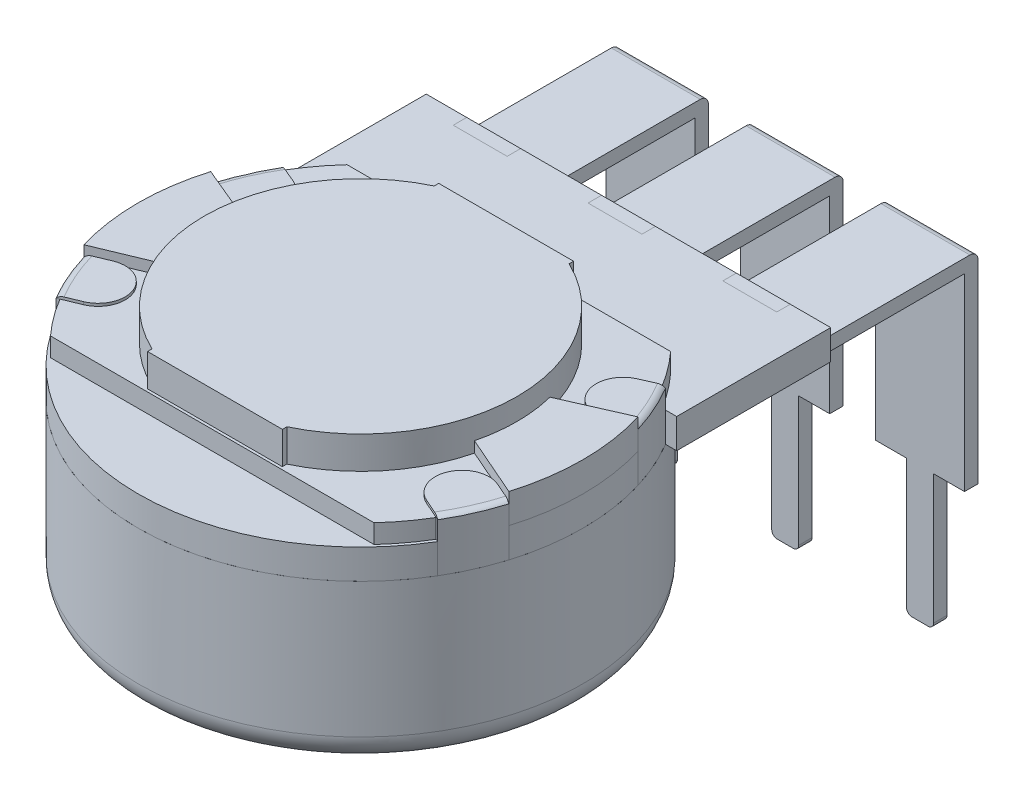
SolidWorks part; units mm, degrees
ref_plane "Front Plane" through (0, 0, 0) normal (0, 0, 1) x (1, 0, 0)
ref_plane "Top Plane" through (0, 0, 0) normal (0, 1, 0) x (1, 0, 0)
ref_plane "Right Plane" through (0, 0, 0) normal (1, 0, 0) x (0, 0, -1)
sketch "Sketch1" plane through (0, 0, 0) normal (0, 1, 0) x (1, 0, 0)
  circle A0 centre (0, 0) radius 8.25
  dimension "D1" = 16.5
extrude "Boss-Extrude1" add sketch "Sketch1" along normal blind 6
fillet "Fillet1" radius 1 1 edges at (0, 0, 8.25)
sketch "Sketch2" plane through (0, 6, 0) normal (0, 1, 0) x (1, 0, 0)
  line L0 (-6, 5.6624) -> (6, 5.6624)
  circle A0 centre (0, 0) radius 8.25 construction
  arc A1 (6, 5.6624) -> (-6, 5.6624) centre (0, 0) ccw
  dimension "D1" = 12
  dimension "D2" = 5.6624
extrude "Cut-Extrude1" cut sketch "Sketch2" against normal blind 2
sketch "Sketch3" plane through (0, 6, 0) normal (0, 1, 0) x (1, 0, 0)
  circle A0 centre (0, 0) radius 8
  dimension "D1" = 16
extrude "Cut-Extrude2" cut sketch "Sketch3" against normal blind 5.6
sketch "Sketch4" plane through (0, 6, 0) normal (0, 1, 0) x (1, 0, 0)
  line L6 (-7.5, 3.4369) -> (-7.5, 9.9369)
  line L7 (-7.5, 9.9369) -> (7.5, 9.9369)
  line L8 (7.5, 3.4369) -> (7.5, 9.9369)
  arc A1 (-6, 5.6624) -> (6, 5.6624) centre (0, 0) ccw construction
  arc A2 (-7.5, 3.4369) -> (7.5, 3.4369) centre (0, 0) ccw
  dimension "D1" = 15
  dimension "D2" = 7.5
  dimension "D3" = 6.5
extrude "Boss-Extrude2" add sketch "Sketch4" along normal blind 1.1 separate body
sketch "Sketch6" plane through (0, 7.1, 0) normal (0, 1, 0) x (1, 0, 0)
  line L1 (-6, 5.5) -> (6, 5.5)
  line L3 (-6, -5.5) -> (6, -5.5)
  arc A0 (-6, 5.5) -> (-6, -5.5) centre (0, 0) ccw
  arc A1 (6, -5.5) -> (6, 5.5) centre (0, 0) ccw
  dimension "D1" = 11
  dimension "D2" = 5.5
  dimension "D3" = 12
  dimension "D4" = 11
extrude "Boss-Extrude3" add sketch "Sketch6" along normal blind 0.7 separate body
sketch "Sketch7" plane through (0, 7.8, 0) normal (0, 1, 0) x (1, 0, 0)
  line L0 (2.5, -5.4) -> (2.5, -5.2335)
  line L1 (-2.5, -5.4) -> (2.5, -5.4)
  line L3 (-2.5, 5.4) -> (2.5, 5.4)
  line L5 (-2.5, -5.4) -> (-2.5, -5.2335)
  line L6 (-2.5, 5.2335) -> (-2.5, 5.4)
  line L7 (2.5, 5.2335) -> (2.5, 5.4)
  arc A0 (-2.5, -5.2335) -> (-2.5, 5.2335) centre (0, 0) cw
  arc A1 (2.5, 5.2335) -> (2.5, -5.2335) centre (0, 0) cw
  dimension "D5" = 5.8
  dimension "D6" = 5.8
  dimension "D1" = 5
  dimension "D2" = 5.4
  dimension "D3" = 10.8
  dimension "D4" = 5.4
  dimension "D7" = 0.1665
  dimension "D8" = 0.1665
extrude "Boss-Extrude4" add sketch "Sketch7" along normal blind 1.2
sketch "Sketch11" plane through (0, 7.1, 0) normal (0, 1, 0) x (1, 0, 0)
  line L2 (-7.9082, 2.35) -> (-5.6294, 1.3965)
  line L3 (-7.9082, -2.35) -> (-5.6276, -1.4035)
  line L4 (7.7928, 2.35) -> (5.6294, 1.3965)
  line L6 (5.6278, -1.4028) -> (7.7928, -2.35)
  arc A0 (-7.5, 3.4369) -> (7.5, 3.4369) centre (0, 0) ccw construction
  arc A1 (-2.5, 5.2335) -> (-2.5, -5.2335) centre (0, 0) ccw construction
  arc A2 (-7.9082, 2.35) -> (-7.9082, -2.35) centre (0, 0) ccw
  arc A3 (-5.6294, 1.3965) -> (-5.6276, -1.4035) centre (0, 0) ccw
  arc A4 (6, -5.5) -> (6, 5.5) centre (0, 0) ccw construction
  arc A5 (2.5, -5.2335) -> (2.5, 5.2335) centre (0, 0) ccw construction
  arc A6 (7.7928, 2.35) -> (7.7928, -2.35) centre (0, 0) cw
  arc A7 (5.6278, -1.4028) -> (5.6294, 1.3965) centre (0, 0) ccw
  dimension "D1" = 4.7
  dimension "D3" = 2.8
extrude "Cut-Extrude4" cut sketch "Sketch11" along normal blind 0.7
sketch "Sketch12" plane through (0, 7.1, 0) normal (0, 1, 0) x (1, 0, 0)
  line L0 (-5.6276, -1.4035) -> (-7.9082, -2.3502)
  line L2 (-7.9082, 2.3502) -> (-5.6294, 1.3965)
  line L4 (5.6294, 1.3965) -> (7.8947, 2.3949)
  line L5 (5.6278, -1.4028) -> (7.8947, -2.3949)
  arc A0 (-2.5, 5.2335) -> (-2.5, -5.2335) centre (0, 0) ccw construction
  arc A1 (-5.6276, -1.4035) -> (-2.5, -5.2335) centre (0, 0) ccw construction
  arc A2 (-7.5, 3.4369) -> (7.5, 3.4369) centre (0, 0) ccw construction
  arc A3 (-5.6294, 1.3965) -> (-5.6276, -1.4035) centre (0, 0) ccw
  arc A4 (-7.9082, 2.3502) -> (-7.9082, -2.3502) centre (0, 0) ccw
  arc A5 (5.6294, 1.3965) -> (5.6278, -1.4028) centre (0, 0) cw
  arc A6 (7.8947, -2.3949) -> (7.8947, 2.3949) centre (0, 0) ccw
extrude "Boss-Extrude6" add sketch "Sketch12" along normal blind 1.1 separate body
sketch "Sketch14" plane through (0, 7.8, 0) normal (0, 1, 0) x (1, 0, 0)
  line L0 (7.8947, -2.3949) -> (7.7928, -2.35)
  line L1 (5.6278, -1.4028) -> (7.7928, -2.35) construction
  line L2 (7.0864, -4.2243) -> (6.9781, -4.1766)
  line L3 (6.9781, -4.1766) -> (7.7928, -2.35)
  line L4 (-7.9082, -2.3502) -> (-7.8055, -2.3074)
  line L5 (-7.8055, -2.3074) -> (-7.0004, -4.1381)
  line L6 (-7.0004, -4.1381) -> (-7.1102, -4.1842)
  line L7 (-7.1102, 4.1842) -> (-7.5, 4.1842)
  line L8 (-7.5, 9.9369) -> (-7.5, 3.4369) construction
  line L9 (-7.5, 4.1842) -> (-7.5, 3.4369)
  line L10 (-7.1102, 4.1842) -> (-7.008, 4.124)
  line L11 (-7.008, 4.124) -> (-7.8056, 2.3071)
  line L12 (-7.8056, 2.3071) -> (-7.9082, 2.3502)
  line L13 (-5.6294, 1.3965) -> (-7.9082, 2.3502) construction
  line L14 (7.0864, 4.2243) -> (7.5, 4.2243)
  line L16 (7.5, 3.4369) -> (7.5, 9.9369) construction
  line L22 (7.5, 4.2243) -> (7.5, 3.4369)
  line L23 (7.0864, 4.2243) -> (6.9858, 4.1644)
  line L24 (6.9858, 4.1644) -> (7.7928, 2.35)
  line L25 (7.8947, 2.3949) -> (5.6294, 1.3965) construction
  line L26 (7.7928, 2.35) -> (5.6294, 1.3965) construction
  line L27 (7.7928, 2.35) -> (7.8947, 2.3949)
  arc A0 (7.8947, -2.3949) -> (7.0864, -4.2243) centre (0, 0) cw
  arc A1 (-7.5, 3.4369) -> (7.5, 3.4369) centre (0, 0) ccw construction
  arc A2 (6, -5.5) -> (7.7928, -2.35) centre (0, 0) ccw construction
  arc A3 (-7.9082, -2.3502) -> (-7.1102, -4.1842) centre (0, 0) ccw
  arc A5 (-7.5, 3.4369) -> (-7.9082, 2.3502) centre (0, 0) ccw
  arc A9 (7.8947, 2.3949) -> (7.5, 3.4369) centre (0, 0) ccw
  point P49 (0, 0)
  dimension "D1" = 2
  dimension "D2" = 2
  dimension "D3" = 2
  dimension "D4" = 2
  dimension "D5" = 0.1191
  dimension "D6" = 2
  dimension "D7" = 1.8169
  dimension "D8" = 0.3898
  dimension "D9" = 2
extrude "Cut-Extrude5" cut sketch "Sketch14" against normal blind 1.8
sketch "Sketch16" plane through (0, 6, 0) normal (0, 1, 0) x (1, 0, 0)
  line L0 (6.9781, -4.1766) -> (7.0864, -4.2243) construction
  line L1 (7.0864, -4.2243) -> (6.9845, -4.1794)
  line L2 (6.9845, -4.1794) -> (7.7927, -2.3503)
  line L3 (7.7927, -2.3503) -> (7.8947, -2.3949)
  line L4 (7.8947, 2.3949) -> (7.7928, 2.35)
  line L5 (7.8947, 2.3949) -> (5.6294, 1.3965) construction
  line L6 (6.9858, 4.1644) -> (7.7928, 2.35) construction
  line L7 (7.7928, 2.35) -> (6.9858, 4.1644)
  line L8 (6.9858, 4.1644) -> (7.0864, 4.2243)
  line L9 (-7.008, 4.124) -> (-7.1102, 4.1842) construction
  line L10 (-7.1102, 4.1842) -> (-7.008, 4.124)
  line L11 (-7.008, 4.124) -> (-7.8056, 2.3071)
  line L12 (-7.8056, 2.3071) -> (-7.9082, 2.3502)
  line L13 (-7.1102, -4.1842) -> (-7.0004, -4.1381) construction
  line L14 (-7.1102, -4.1842) -> (-7.0004, -4.1381)
  line L15 (-7.0004, -4.1381) -> (-7.8055, -2.3074)
  line L16 (-7.8055, -2.3074) -> (-7.9082, -2.3502)
  arc A0 (7.8947, -2.3949) -> (7.0864, -4.2243) centre (0, 0) cw
  arc A1 (7.0864, 4.2243) -> (7.8947, 2.3949) centre (0, 0) cw
  arc A2 (7.8947, -2.3949) -> (7.8947, 2.3949) centre (0, 0) ccw construction
  arc A3 (-7.9082, 2.3502) -> (-7.1102, 4.1842) centre (0, 0) cw
  arc A4 (-7.9082, -2.3502) -> (-7.1102, -4.1842) centre (0, 0) ccw
  arc A5 (-6, 5.6624) -> (6, 5.6624) centre (0, 0) ccw construction
extrude "Boss-Extrude7" add sketch "Sketch16" along normal blind 1.8 separate body
sketch "Sketch17" plane through (0, 7.8, 0) normal (0, 1, 0) x (1, 0, 0)
  line L0 (-7.008, 4.124) -> (-7.1102, 4.1842) construction
  line L2 (-7.1102, 4.1842) -> (-5.4498, 3.4892)
  line L3 (-7.9082, 2.3502) -> (-6.2477, 1.6553)
  line L4 (-5.4498, 3.4892) -> (-6.2477, 1.6553)
  line L5 (-5.6294, 1.3965) -> (-7.9082, 2.3502) construction
  line L7 (-7.1102, -4.1842) -> (-5.4478, -3.494)
  line L8 (-7.9082, -2.3502) -> (-6.2457, -1.66)
  line L9 (-5.4478, -3.494) -> (-6.2457, -1.66)
  line L10 (-7.8055, -2.3074) -> (-5.6276, -1.4035) construction
  line L11 (5.6278, -1.4028) -> (7.8947, -2.3949) construction
  line L13 (7.0864, -4.2243) -> (5.435, -3.5016)
  line L14 (7.8947, -2.3949) -> (6.2433, -1.6722)
  line L15 (5.435, -3.5016) -> (6.2433, -1.6722)
  line L16 (7.0864, 4.2243) -> (6.9858, 4.1644) construction
  line L18 (7.0864, 4.2243) -> (5.435, 3.4965)
  line L19 (7.8947, 2.3949) -> (6.2416, 1.6663)
  line L20 (5.435, 3.4965) -> (6.2416, 1.6663)
  line L21 (7.8947, 2.3949) -> (5.6294, 1.3965) construction
  arc A0 (-7.9082, 2.3502) -> (-7.1102, 4.1842) centre (0, 0) cw
  arc A1 (-7.9082, -2.3502) -> (-7.1102, -4.1842) centre (0, 0) ccw
  arc A2 (-7.1102, -4.1842) -> (7.0864, -4.2243) centre (0, 0) ccw construction
  arc A3 (7.0864, -4.2243) -> (7.8947, -2.3949) centre (0, 0) ccw
  arc A4 (7.8947, 2.3949) -> (7.0864, 4.2243) centre (0, 0) ccw
  dimension "D1" = 1.8
  dimension "D2" = 2
  dimension "D3" = 1.8
  dimension "D4" = 1.8
  dimension "D5" = 2
  dimension "D6" = 1.8027
  dimension "D7" = 1.8048
  dimension "D8" = 2
  dimension "D9" = 2
extrude "Boss-Extrude11" add sketch "Sketch17" along normal blind 0.1 separate body
fillet "Fillet8" radius 0.3 1 edges at (-7.565, 7.9, -3.2915)
fillet "Fillet9" radius 0.3 1 edges at (-7.565, 7.9, 3.2915)
fillet "Fillet10" radius 0.3 1 edges at (7.5462, 7.9, 3.3342)
fillet "Fillet12" radius 0.3 1 edges at (7.5462, 7.9, -3.3342)
fillet "Fillet13" radius 1 1 edges at (-5.4478, 7.85, 3.494)
fillet "Fillet14" radius 1 1 edges at (-6.2457, 7.85, 1.66)
fillet "Fillet16" radius 1 1 edges at (-5.4498, 7.85, -3.4892)
fillet "Fillet17" radius 1 1 edges at (-6.2477, 7.85, -1.6553)
fillet "Fillet18" radius 1 1 edges at (5.435, 7.85, 3.5016)
fillet "Fillet19" radius 1 1 edges at (6.2433, 7.85, 1.6722)
fillet "Fillet20" radius 1 1 edges at (5.435, 7.85, -3.4965)
fillet "Fillet21" radius 1 1 edges at (6.2416, 7.85, -1.6663)
sketch "Sketch18" plane through (0, 6, 0) normal (0, -1, 0) x (1, 0, 0)
  line L0 (7.5, -9.9369) -> (-7.5, -9.9369) construction
  line L2 (-1.75, -9.9369) -> (-1.75, -5.9369)
  line L3 (-1.75, -5.9369) -> (1.75, -5.9369)
  line L4 (1.75, -9.9369) -> (1.75, -5.9369)
  line L5 (-1.75, -9.9369) -> (-1.65, -9.9369)
  line L7 (-1.65, -9.9369) -> (-1.65, -16.25)
  line L8 (-1.65, -16.25) -> (1.65, -16.25)
  line L9 (1.65, -9.9369) -> (1.65, -16.25)
  line L10 (1.65, -9.9369) -> (1.75, -9.9369)
  line L11 (3.25, -9.9369) -> (3.35, -9.9369)
  line L12 (3.25, -5.9369) -> (6.75, -5.9369)
  line L13 (3.25, -5.9369) -> (3.25, -9.9369)
  line L15 (6.75, -5.9369) -> (6.75, -9.9369)
  line L17 (3.35, -9.9369) -> (3.35, -16.25)
  line L18 (3.35, -16.25) -> (6.65, -16.25)
  line L19 (6.65, -9.9369) -> (6.65, -16.25)
  line L20 (6.65, -9.9369) -> (6.75, -9.9369)
  line L21 (-6.75, -9.9369) -> (-6.65, -9.9369)
  line L22 (-3.25, -5.9369) -> (-6.75, -5.9369)
  line L23 (-3.25, -5.9369) -> (-3.25, -9.9369)
  line L25 (-6.75, -5.9369) -> (-6.75, -9.9369)
  line L27 (-6.65, -9.9369) -> (-6.65, -16.25)
  line L28 (-6.65, -16.25) -> (-3.35, -16.25)
  line L29 (-3.35, -9.9369) -> (-3.35, -16.25)
  line L30 (-3.35, -9.9369) -> (-3.25, -9.9369)
  dimension "D1" = 1.75
  dimension "D2" = 1.75
  dimension "D3" = 4
  dimension "D4" = 0.1
  dimension "D5" = 0.1
  dimension "D6" = 16.25
  dimension "D7" = 4
  dimension "D8" = 1.5
  dimension "D9" = 3.5
  dimension "D10" = 4
  dimension "D11" = 0.1
  dimension "D12" = 0.1
  dimension "D13" = 16.25
  dimension "D14" = 1.5
  dimension "D15" = 3.5
  dimension "D17" = 0.1
  dimension "D18" = 0.1
  dimension "D19" = 16.25
extrude "Boss-Extrude12" add sketch "Sketch18" along normal blind 0.5 separate body
sketch "Sketch19" plane through (0, 5.5, 0) normal (0, -1, 0) x (1, 0, 0)
  line L0 (-3.35, -16.25) -> (-3.35, -9.9369) construction
  line L1 (-6.65, -16.25) -> (-3.35, -16.25)
  line L2 (-6.65, -16.25) -> (-6.65, -15.75)
  line L3 (-6.65, -15.75) -> (-3.35, -15.75)
  line L4 (-3.35, -16.25) -> (-3.35, -15.75)
  line L5 (1.65, -16.25) -> (1.65, -9.9369) construction
  line L6 (-1.65, -16.25) -> (1.65, -16.25)
  line L7 (-1.65, -16.25) -> (-1.65, -15.75)
  line L8 (-1.65, -15.75) -> (1.65, -15.75)
  line L9 (1.65, -16.25) -> (1.65, -15.75)
  line L10 (6.65, -16.25) -> (6.65, -9.9369) construction
  line L11 (3.35, -16.25) -> (6.65, -16.25)
  line L12 (3.35, -16.25) -> (3.35, -15.75)
  line L13 (3.35, -15.75) -> (6.65, -15.75)
  line L14 (6.65, -16.25) -> (6.65, -15.75)
  dimension "D1" = 0.5
  dimension "D2" = 0.5
  dimension "D3" = 0.5
extrude "Boss-Extrude13" add sketch "Sketch19" along normal blind 12
sketch "Sketch20" plane through (0, 0, -16.25) normal (0, 0, -1) x (-1, 0, 0)
  line L0 (-6.65, -6.5) -> (-6.65, 6) construction
  line L1 (-6.65, -1.5) -> (-5.5, -1.5)
  line L2 (-6.65, -1.5) -> (-6.65, -6.5)
  line L3 (-6.65, -6.5) -> (-5.5, -6.5)
  line L4 (-5.5, -1.5) -> (-5.5, -6.5)
  line L5 (-3.35, -6.5) -> (-6.65, -6.5) construction
  line L6 (-3.35, -6.5) -> (-3.35, 6) construction
  line L7 (-4.5, -6.5) -> (-3.35, -6.5)
  line L8 (-4.5, -6.5) -> (-4.5, -1.5)
  line L9 (-4.5, -1.5) -> (-3.35, -1.5)
  line L10 (-3.35, -6.5) -> (-3.35, -1.5)
  line L11 (-1.65, -6.5) -> (-1.65, 6) construction
  line L12 (-1.65, -1.5) -> (-0.5, -1.5)
  line L13 (-1.65, -1.5) -> (-1.65, -6.5)
  line L14 (-1.65, -6.5) -> (-0.5, -6.5)
  line L15 (-0.5, -1.5) -> (-0.5, -6.5)
  line L16 (1.65, -6.5) -> (-1.65, -6.5) construction
  line L17 (1.65, -6.5) -> (1.65, 6) construction
  line L18 (1.65, -1.5) -> (0.5, -1.5)
  line L19 (1.65, -1.5) -> (1.65, -6.5)
  line L20 (1.65, -6.5) -> (0.5, -6.5)
  line L21 (0.5, -1.5) -> (0.5, -6.5)
  line L23 (3.35, -6.5) -> (4.5, -6.5)
  line L24 (3.35, -6.5) -> (3.35, -1.5)
  line L25 (3.35, -1.5) -> (4.5, -1.5)
  line L26 (4.5, -6.5) -> (4.5, -1.5)
  line L27 (6.65, -6.5) -> (5.5, -6.5)
  line L28 (6.65, -6.5) -> (6.65, -1.5)
  line L29 (6.65, -1.5) -> (5.5, -1.5)
  line L30 (5.5, -6.5) -> (5.5, -1.5)
  dimension "D1" = 1
  dimension "D2" = 1.15
  dimension "D3" = 5
  dimension "D4" = 5
  dimension "D5" = 1
  dimension "D6" = 1.15
  dimension "D7" = 5
  dimension "D8" = 5
  dimension "D9" = 1
  dimension "D10" = 1.15
  dimension "D11" = 5
  dimension "D12" = 5
extrude "Cut-Extrude6" cut sketch "Sketch20" against normal blind 0.5
fillet "Fillet22" radius 0.2 1 edges at (5.5, -6.5, -16)
fillet "Fillet23" radius 0.2 1 edges at (0.5, -6.5, -16)
fillet "Fillet24" radius 0.2 1 edges at (-4.5, -6.5, -16)
fillet "Fillet25" radius 0.2 1 edges at (-5.5, -6.5, -16)
fillet "Fillet26" radius 0.2 1 edges at (-0.5, -6.5, -16)
fillet "Fillet27" radius 0.2 1 edges at (4.5, -6.5, -16)
fillet "Fillet28" radius 0.3 1 edges at (-5, 6, -16.25)
fillet "Fillet29" radius 0.3 1 edges at (0, 6, -16.25)
fillet "Fillet30" radius 0.3 1 edges at (5, 6, -16.25)
fillet "Fillet32" radius 1.75 1 edges at (6.75, 5.75, -5.9369)
fillet "Fillet33" radius 1.75 1 edges at (3.25, 5.75, -5.9369)
fillet "Fillet34" radius 1.75 1 edges at (-1.75, 5.75, -5.9369)
fillet "Fillet35" radius 1.75 1 edges at (-6.75, 5.75, -5.9369)
fillet "Fillet36" radius 1.75 1 edges at (1.75, 5.75, -5.9369)
fillet "Fillet37" radius 1.75 1 edges at (-3.25, 5.75, -5.9369)
sketch "Sketch21" plane through (0, 5.5, 0) normal (0, -1, 0) x (1, 0, 0)
  line L0 (7.5, -9.9369) -> (-7.5, -9.9369) construction
  line L1 (-6, -9.4369) -> (-4, -9.4369)
  line L2 (-6, -9.4369) -> (-6, -10.9369)
  line L3 (-6, -10.9369) -> (-4, -10.9369)
  line L4 (-4, -9.4369) -> (-4, -10.9369)
  line L5 (-3.35, -15.75) -> (-3.35, -9.9369) construction
  line L6 (1.65, -15.75) -> (1.65, -9.9369) construction
  line L7 (-1, -9.4369) -> (1, -9.4369)
  line L8 (-1, -9.4369) -> (-1, -10.9369)
  line L9 (-1, -10.9369) -> (1, -10.9369)
  line L10 (1, -9.4369) -> (1, -10.9369)
  line L11 (3.35, -9.9369) -> (3.35, -15.75) construction
  line L12 (4, -9.4369) -> (6, -9.4369)
  line L13 (4, -9.4369) -> (4, -10.9369)
  line L14 (4, -10.9369) -> (6, -10.9369)
  line L15 (6, -9.4369) -> (6, -10.9369)
  dimension "D1" = 0.5
  dimension "D2" = 2
  dimension "D3" = 0.65
  dimension "D4" = 1.5
  dimension "D5" = 0.5
  dimension "D6" = 0.65
  dimension "D7" = 2
  dimension "D8" = 1.5
  dimension "D9" = 0.5
  dimension "D10" = 0.65
  dimension "D11" = 2
  dimension "D12" = 1.5
extrude "Cut-Extrude7" cut sketch "Sketch21" against normal blind 1.6
sketch "Sketch22" plane through (0, 0, -9.4369) normal (0, 0, -1) x (-1, 0, 0)
  line L0 (-5, 5.5) -> (-3.25, 5.5) construction
  line L1 (-6, 7.1) -> (-4, 7.1)
  line L2 (-6, 7.1) -> (-6, 5.5)
  line L3 (-6, 5.5) -> (-4, 5.5)
  line L4 (-4, 7.1) -> (-4, 5.5)
  line L5 (-4, 6) -> (-4, 5.5) construction
  line L6 (6, 4) -> (6, 6) construction
  line L7 (-1, 7.1) -> (1, 7.1)
  line L8 (-1, 7.1) -> (-1, 5.5)
  line L9 (-1, 5.5) -> (1, 5.5)
  line L10 (1, 7.1) -> (1, 5.5)
  line L11 (4, 7.1) -> (6, 7.1)
  line L12 (4, 7.1) -> (4, 5.5)
  line L13 (4, 5.5) -> (6, 5.5)
  line L14 (6, 7.1) -> (6, 5.5)
  line L15 (4, 5.5) -> (6, 5.5) construction
extrude "Boss-Extrude14" add sketch "Sketch22" along normal blind 0.5 separate body
fillet "Fillet38" radius 0.2 1 edges at (5, 5.5, -9.9369)
fillet "Fillet39" radius 0.2 1 edges at (0, 5.5, -9.9369)
fillet "Fillet40" radius 0.2 1 edges at (-5, 5.5, -9.9369)
